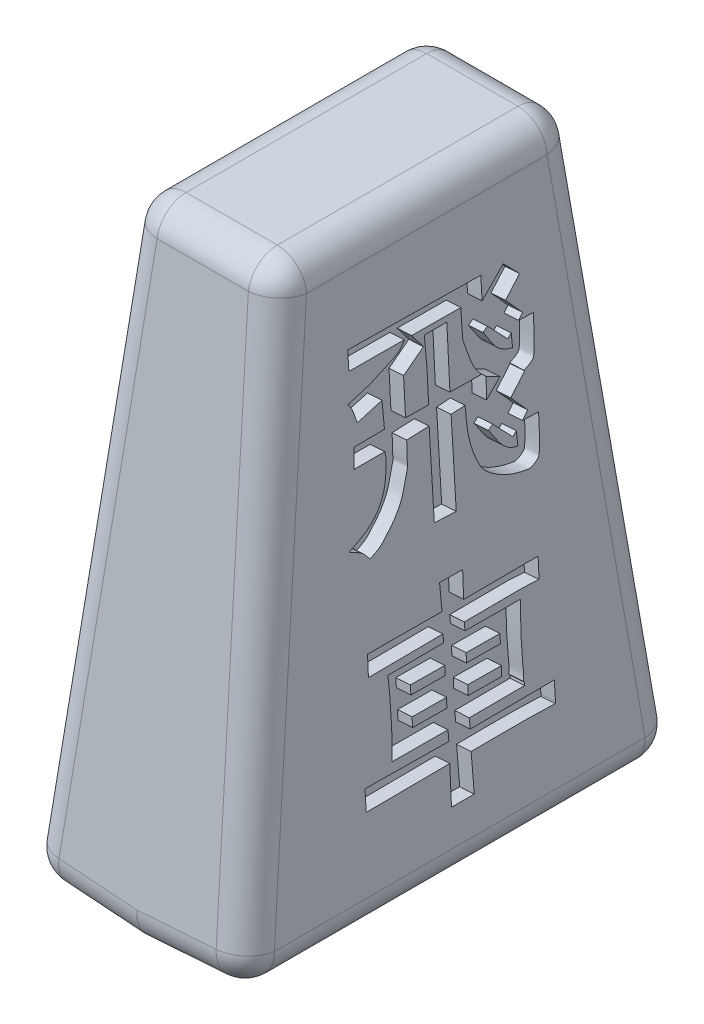
SolidWorks part; units mm, degrees
ref_plane "Płaszczyzna przednia" through (0, 0, 0) normal (0, 0, 1) x (1, 0, 0)
ref_plane "Płaszczyzna górna" through (0, 0, 0) normal (0, 1, 0) x (1, 0, 0)
ref_plane "Płaszczyzna prawa" through (0, 0, 0) normal (1, 0, 0) x (0, 0, -1)
sketch "Szkic1" plane through (0, 0, 0) normal (0, 0, 1) x (1, 0, 0)
  line L0 (0, 0) -> (0, 40)
  line L1 (3.1225, 40) -> (-3.1225, 40)
  line L2 (-5.1185, 38.1262) -> (-7.3738, 2.4704)
  line L3 (-5.504, 0.3481) -> (0, 0)
  line L4 (5.504, 0.3481) -> (0, 0)
  line L5 (5.1185, 38.1262) -> (7.3738, 2.4704)
  arc A0 (-3.1225, 40) -> (-5.1185, 38.1262) centre (-3.1225, 38) ccw
  arc A1 (-7.3738, 2.4704) -> (-5.504, 0.3481) centre (-5.3777, 2.3441) ccw
  arc A2 (7.3738, 2.4704) -> (5.504, 0.3481) centre (5.3777, 2.3441) cw
  arc A3 (3.1225, 40) -> (5.1185, 38.1262) centre (3.1225, 38) cw
  point P7 (-5, 40)
  point P10 (-7.5, 0.4744)
  point P17 (7.5, 0.4744)
  point P18 (5, 40)
  dimension "D5" = 2
  dimension "D1" = 40
  dimension "D2" = 90
  dimension "D3" = 5
  dimension "D4" = 7.5
extrude "Dodanie-wyciągnięcie1" add sketch "Szkic1" along normal blind 30 contours L2 A1 L3 L0 L1 A0 | A3 L1 L0 L4 A2 L5 region at (-3.1441, 18.7866, 0) region at (3.1441, 18.7866, 0)
ref_plane "Płaszczyzna1" through (5.1225, 0, 0) normal (1, 0, 0) x (0, 0, -1)
ref_plane "Płaszczyzna2" through (15.1225, 0, 0) normal (1, 0, 0) x (0, 0, -1)
sketch "Szkic7" plane through (15.1225, 0, 0) normal (1, 0, 0) x (0, 0, -1)
  line L0 (-25, 40) -> (-5, 40)
  line L1 (-30, 40) -> (0, 40) construction
  line L2 (-5, 40) -> (0, 0)
  line L3 (0, 0) -> (-30, 0)
  line L4 (-30, 0) -> (0, 0) construction
  line L5 (-15, 0) -> (-15, 40)
  line L6 (-25, 40) -> (-30, 0)
  line L8 (0, 0) -> (-30, 0)
  line L9 (0, 0) -> (0, 40)
  line L10 (0, 40) -> (-30, 40)
  line L11 (-30, 0) -> (-30, 40)
  dimension "D1" = 10
  dimension "D2" = 15
  dimension "D3" = 40
extrude "Wytnij-wyciągnięcie11" cut sketch "Szkic7" against normal through all and the other way through all contours L11 L6 L10 | L9 L10 L2 region at (15.1225, 26.6667, 28.3333) region at (15.1225, 26.6667, 1.6667)
fillet "Zaokrąglenie2" radius 2 18 edges at (0, 40, 5) (-4.4914, 39.4582, 4.9323) (-6.2461, 20.2983, 2.5373) (-6.8784, 1.022, 0.1278) (-2.752, 0.1741, 0.0218) (2.752, 0.1741, 0.0218) (6.8784, 1.022, 0.1278) (6.2461, 20.2983, 2.5373) (4.4914, 39.4582, 4.9323) (4.4914, 39.4582, 25.0677) (6.2461, 20.2983, 27.4627) (6.8784, 1.022, 29.8722) (2.752, 0.1741, 29.9782) (-2.752, 0.1741, 29.9782) (-6.8784, 1.022, 29.8722) (-6.2461, 20.2983, 27.4627) (-4.4914, 39.4582, 25.0677) (0, 40, 25)
sketch "Szkic8" plane through (-7.5, 0.4744, 0) normal (-0.998, 0.0631, 0) x (0, 0, 1)
  line L0 (341.3333, 1024) -> (1706.6667, 1024) construction
  line L1 (9.2738, 33.1189) -> (18.3738, 32.9989)
  line L2 (18.3738, 32.9989) -> (18.3538, 31.4989)
  line L3 (18.3538, 31.4989) -> (19.9138, 32.8989)
  line L4 (19.9138, 32.8989) -> (20.9538, 31.8389)
  line L5 (20.9538, 31.8389) -> (19.9338, 30.7989)
  line L6 (19.9338, 30.7989) -> (21.0138, 29.5789)
  line L7 (21.0138, 29.5789) -> (20.7338, 29.2589)
  line L8 (20.7338, 29.2589) -> (21.7338, 29.2189)
  line L9 (20.9138, 26.2989) -> (20.9538, 26.2389)
  line L10 (20.9538, 26.2389) -> (19.9338, 25.1789)
  line L11 (19.9338, 25.1789) -> (21.0138, 23.9589)
  line L12 (21.0138, 23.9589) -> (20.6338, 23.5389)
  line L13 (20.6338, 23.5389) -> (21.7338, 23.4989)
  line L14 (16.8738, 26.2389) -> (15.9138, 26.1789)
  line L15 (15.9138, 26.1789) -> (15.9138, 20.5989)
  line L16 (15.9138, 20.5989) -> (14.4138, 20.6589)
  line L17 (14.4138, 20.6589) -> (14.4138, 26.2389)
  line L18 (14.4138, 26.2389) -> (12.8738, 26.1789)
  line L19 (11.3738, 26.2389) -> (9.2738, 26.2389)
  line L20 (9.2738, 26.2389) -> (9.3338, 27.4789)
  line L21 (9.3338, 27.4789) -> (11.4338, 27.4989)
  line L22 (11.4338, 27.4989) -> (11.3738, 29.1989)
  line L23 (11.3738, 29.1989) -> (9.6538, 28.7389)
  line L24 (13.0738, 31.8589) -> (9.2738, 31.8789)
  line L25 (9.2738, 31.8789) -> (9.2738, 33.1189)
  line L26 (13.5738, 31.8589) -> (16.9338, 31.8389)
  line L27 (18.0738, 27.4389) -> (15.9138, 27.4589)
  line L28 (15.9138, 27.4589) -> (15.9538, 31.4789)
  line L29 (15.9538, 31.4789) -> (14.4738, 31.4789)
  line L30 (14.4738, 31.4789) -> (14.4138, 31.4589)
  line L31 (14.4538, 27.4389) -> (12.8738, 27.4589)
  line L32 (12.8738, 27.4589) -> (12.8938, 29.8789)
  line L33 (12.8938, 29.8789) -> (14.3138, 30.8589)
  line L34 (14.3138, 30.8589) -> (13.5738, 31.8589)
  line L35 (18.6338, 29.9389) -> (19.9338, 28.5789)
  line L36 (19.9338, 28.5789) -> (20.1938, 28.7989)
  line L37 (20.1938, 28.7989) -> (20.2338, 27.9189)
  line L38 (18.3338, 29.7189) -> (18.6338, 29.9389)
  line L39 (18.3738, 27.1789) -> (19.2938, 26.7189)
  line L40 (19.2938, 26.7189) -> (18.2938, 25.8389)
  line L41 (18.2938, 25.8389) -> (18.3738, 27.1789)
  line L42 (18.6138, 24.2989) -> (19.9338, 22.9389)
  line L43 (19.9338, 22.9389) -> (20.1738, 23.1589)
  line L44 (20.1738, 23.1589) -> (20.2338, 22.2589)
  line L45 (18.3538, 24.0789) -> (18.3338, 24.0789)
  line L46 (18.3338, 24.0789) -> (18.6138, 24.2789)
  line L47 (18.6138, 24.2789) -> (18.6138, 24.2989)
  line L48 (14.5538, 17.1589) -> (16.1338, 17.1189)
  line L49 (16.1338, 17.1189) -> (16.0938, 15.4389)
  line L50 (16.0938, 15.4389) -> (21.1938, 15.4389)
  line L51 (21.1938, 15.4389) -> (21.1538, 14.1189)
  line L52 (16.0538, 14.1389) -> (16.0938, 13.6389)
  line L53 (16.0938, 13.6389) -> (19.8738, 13.5989)
  line L54 (19.8338, 8.6589) -> (16.0538, 8.6189)
  line L55 (16.0538, 8.6189) -> (16.0938, 7.9789)
  line L56 (16.0938, 7.9789) -> (21.8138, 8.0389)
  line L57 (21.8138, 8.0389) -> (21.7938, 6.6789)
  line L58 (21.7938, 6.6789) -> (16.0538, 6.6789)
  line L59 (16.0538, 6.6789) -> (16.1138, 4.2189)
  line L60 (16.1138, 4.2189) -> (14.5538, 4.2589)
  line L61 (14.5538, 4.2589) -> (14.5938, 6.7189)
  line L62 (14.5938, 6.7189) -> (8.8738, 6.6589)
  line L63 (8.8738, 6.6589) -> (8.9138, 8.0389)
  line L64 (14.6138, 8.0189) -> (14.5738, 8.6589)
  line L65 (14.5738, 8.6589) -> (10.7738, 8.6989)
  line L66 (10.7938, 13.6389) -> (14.6138, 13.6789)
  line L67 (14.6138, 13.6789) -> (14.5738, 14.1789)
  line L68 (14.5738, 14.1789) -> (9.5138, 14.1189)
  line L69 (9.5138, 14.1189) -> (9.5338, 15.4789)
  line L70 (9.5338, 15.4789) -> (14.6138, 15.4789)
  line L71 (14.6138, 15.4789) -> (14.5538, 17.1589)
  line L72 (12.2538, 12.3789) -> (14.6138, 12.3589)
  line L73 (14.6138, 12.3589) -> (14.5938, 11.7789)
  line L74 (14.5938, 11.7789) -> (12.2538, 11.7989)
  line L75 (12.2538, 11.7989) -> (12.2538, 12.3789)
  line L76 (16.0738, 12.3789) -> (18.3938, 12.3589)
  line L77 (18.3938, 12.3589) -> (18.3738, 11.7789)
  line L78 (18.3738, 11.7789) -> (16.0538, 11.7989)
  line L79 (16.0538, 11.7989) -> (16.0738, 12.3789)
  line L80 (12.2538, 10.5389) -> (14.6138, 10.5189)
  line L81 (14.6138, 10.5189) -> (14.5938, 9.8989)
  line L82 (14.5938, 9.8989) -> (12.2538, 9.9189)
  line L83 (12.2538, 9.9189) -> (12.2538, 10.5389)
  line L84 (16.0738, 10.5389) -> (18.3738, 10.5189)
  line L85 (18.3738, 10.5189) -> (18.3538, 9.8989)
  line L86 (18.3538, 9.8989) -> (16.0538, 9.9189)
  line L87 (16.0538, 9.9189) -> (16.0738, 10.5389)
  spline S0 degree 3 poles (21.7338, 29.2189) (21.6938, 28.4189) (21.7556, 27.6073) (21.6138, 26.8189) (21.5631, 26.5367) (21.1305, 26.3937) (20.9138, 26.2989) knots 0 0 0 0 1 1 1 2 2 2 2
  spline S1 degree 3 poles (21.7338, 23.4989) (21.6938, 22.6989) (21.7511, 21.8881) (21.6138, 21.0989) (21.5848, 20.9317) (21.401, 20.8235) (21.2538, 20.7389) (21.1235, 20.664) (20.9627, 20.6174) (20.8138, 20.6389) (20.3497, 20.706) (19.888, 20.8218) (19.4538, 20.9989) (19.0473, 21.1648) (18.6627, 21.3924) (18.3138, 21.6589) (18.0626, 21.8509) (17.8251, 22.0813) (17.6738, 22.3589) (17.2582, 23.1222) (17.0152, 23.9937) (16.9338, 24.8589) (16.8907, 25.3174) (16.8938, 25.7789) (16.8738, 26.2389) knots 0 0 0 0 1 1 1 2 2 2 3 3 3 4 4 4 5 5 5 6 6 6 7 7 7 8 8 8 8
  spline S2 degree 3 poles (12.8738, 26.1789) (12.8405, 25.6056) (12.8125, 25.0319) (12.7738, 24.4589) (12.7724, 24.4379) (12.7603, 24.419) (12.7538, 24.3989) (12.6069, 23.939) (12.5242, 23.4535) (12.3138, 23.0189) (12.1132, 22.6045) (11.8406, 22.2223) (11.5338, 21.8789) (11.2222, 21.53) (10.8458, 21.2428) (10.4738, 20.9589) (10.3364, 20.854) (10.1672, 20.7989) (10.0138, 20.7189) knots 0 0 0 0 1 1 1 2 2 2 3 3 3 4 4 4 5 5 5 6 6 6 6
  spline S3 degree 3 poles (10.0138, 20.7189) (9.8472, 20.9056) (9.7126, 21.1269) (9.5138, 21.2789) (9.2531, 21.4784) (8.9405, 21.5989) (8.6538, 21.7589) knots 0 0 0 0 1 1 1 2 2 2 2
  spline S4 degree 3 poles (8.6538, 21.7589) (9.0738, 21.9789) (9.524, 22.1491) (9.9138, 22.4189) (10.224, 22.6337) (10.5139, 22.8924) (10.7338, 23.1989) (10.9616, 23.5164) (11.1285, 23.8827) (11.2338, 24.2589) (11.3645, 24.7256) (11.3997, 25.2155) (11.4338, 25.6989) (11.4466, 25.8796) (11.3938, 26.0589) (11.3738, 26.2389) knots 0 0 0 0 1 1 1 2 2 2 3 3 3 4 4 4 5 5 5 5
  spline S5 degree 3 poles (9.6538, 28.7389) (9.5605, 29.0256) (9.4916, 29.3214) (9.3738, 29.5989) (9.3037, 29.7642) (9.1872, 29.9056) (9.0938, 30.0589) knots 0 0 0 0 1 1 1 2 2 2 2
  spline S6 degree 3 poles (9.0938, 30.0589) (9.7405, 30.2523) (10.4158, 30.3677) (11.0338, 30.6389) (12.7351, 31.3854) (12.5704, 31.1876) (13.0738, 31.8589) knots 0 0 0 0 1 1 1 2 2 2 2
  spline S7 degree 3 poles (16.9338, 31.8389) (16.9405, 31.2256) (16.9407, 30.6122) (16.9538, 29.9989) (16.954, 29.9895) (16.9716, 29.9881) (16.9738, 29.9789) (17.0221, 29.786) (17.0537, 29.6192) (17.1138, 29.4389) (17.4038, 28.5692) (17.4914, 28.0941) (18.0738, 27.4389) knots 0 0 0 0 1 1 1 2 2 2 3 3 3 4 4 4 4
  spline S8 degree 3 poles (14.4138, 31.4589) (14.4338, 30.8189) (14.4675, 30.1792) (14.4738, 29.5389) (14.4808, 28.8389) (14.4605, 28.1389) (14.4538, 27.4389) knots 0 0 0 0 1 1 1 2 2 2 2
  spline S9 degree 3 poles (20.2338, 27.9189) (19.0646, 28.2112) (18.9385, 28.812) (18.3338, 29.7189) knots 0 0 0 0 1 1 1 1
  spline S10 degree 3 poles (20.2338, 22.2589) (19.1886, 22.449) (18.8732, 23.2998) (18.3538, 24.0789) knots 0 0 0 0 1 1 1 1
  spline S11 degree 3 poles (21.1538, 14.1189) (20.1272, 14.1389) (19.1007, 14.1749) (18.0738, 14.1789) (17.4004, 14.1816) (16.7272, 14.1523) (16.0538, 14.1389) knots 0 0 0 0 1 1 1 2 2 2 2
  spline S12 degree 3 poles (19.8738, 13.5989) (19.8405, 12.6456) (19.7816, 11.6928) (19.7738, 10.7389) (19.7682, 10.0453) (19.8138, 9.3523) (19.8338, 8.6589) knots 0 0 0 0 1 1 1 2 2 2 2
  spline S13 degree 3 poles (8.9138, 8.0389) (9.9005, 8.0189) (10.887, 7.9824) (11.8738, 7.9789) (12.7873, 7.9757) (13.7005, 8.0056) (14.6138, 8.0189) knots 0 0 0 0 1 1 1 2 2 2 2
  spline S14 degree 3 poles (10.7738, 8.6989) (10.8077, 9.6054) (10.8859, 10.5125) (10.8538, 11.4189) (10.8277, 12.1587) (10.8138, 12.8989) (10.7938, 13.6389) knots 0 0 0 0 1 1 1 2 2 2 2
extrude "Wytnij-wyciągnięcie12" cut sketch "Szkic8" against normal blind 1 contours S6 S5 L23 L22 L21 L20 L19 S4 S3 S2 L18 L17 L16 L15 L14 S1 L13 L12 L11 L10 L9 S0 L8 L7 L6 L5 L4 L3 L2 L1 L25 L24 L40 L41 L39 L30 S8 L31 L32 L33 L34 L26 S7 L27 L28 L29 L37 S9 | S14 L65 L64 S13 L63 L62 L61 L60 L59 L58 L57 L56 L55 L54 S12 L53 L52 S11 L51 L50 L49 L48 L71 L70 L69 L68 L67 L66 L86 L87 L84 L85 L82 L83 L80 L81 L78 L79 L76 L77 L74 L75 L72 L73 region at (-5.7894, 27.5195, 15.8388) region at (-6.81, 11.3834, 15.3264)
sketch "Szkic9" plane through (7.5, 0.4744, 0) normal (0.998, 0.0631, 0) x (0, 0, -1)
  line L0 (341.3333, 1024) -> (1706.6667, 1024) construction
  line L1 (-20.694, 33.2496) -> (-11.594, 33.1296)
  line L2 (-11.594, 33.1296) -> (-11.594, 31.6496)
  line L3 (-11.594, 31.6496) -> (-10.054, 33.0496)
  line L4 (-10.054, 33.0496) -> (-9.014, 31.9696)
  line L5 (-9.014, 31.9696) -> (-10.034, 30.9296)
  line L6 (-10.034, 30.9296) -> (-8.954, 29.7096)
  line L7 (-8.954, 29.7096) -> (-9.234, 29.3896)
  line L8 (-9.234, 29.3896) -> (-8.234, 29.3496)
  line L9 (-9.054, 26.4296) -> (-9.014, 26.3696)
  line L10 (-9.014, 26.3696) -> (-10.034, 25.3096)
  line L11 (-10.034, 25.3096) -> (-8.954, 24.0896)
  line L12 (-8.954, 24.0896) -> (-9.334, 23.6696)
  line L13 (-9.334, 23.6696) -> (-8.234, 23.6296)
  line L14 (-13.094, 26.3696) -> (-14.054, 26.3096)
  line L15 (-14.054, 26.3096) -> (-14.054, 20.7296)
  line L16 (-14.054, 20.7296) -> (-15.554, 20.7896)
  line L17 (-15.554, 20.7896) -> (-15.554, 26.3696)
  line L18 (-15.554, 26.3696) -> (-17.094, 26.3096)
  line L19 (-18.594, 26.3696) -> (-20.694, 26.3696)
  line L20 (-20.694, 26.3696) -> (-20.634, 27.6096)
  line L21 (-20.634, 27.6096) -> (-18.534, 27.6296)
  line L22 (-18.534, 27.6296) -> (-18.594, 29.3296)
  line L23 (-18.594, 29.3296) -> (-20.314, 28.8696)
  line L24 (-16.894, 31.9896) -> (-20.694, 32.0096)
  line L25 (-20.694, 32.0096) -> (-20.694, 33.2496)
  line L26 (-16.394, 31.9896) -> (-13.034, 31.9696)
  line L27 (-11.894, 27.5696) -> (-14.054, 27.5896)
  line L28 (-14.054, 27.5896) -> (-14.014, 31.6096)
  line L29 (-14.014, 31.6096) -> (-15.494, 31.6096)
  line L30 (-15.494, 31.6096) -> (-15.554, 31.5896)
  line L31 (-15.514, 27.5696) -> (-17.094, 27.5896)
  line L32 (-17.094, 27.5896) -> (-17.074, 30.0096)
  line L33 (-17.074, 30.0096) -> (-15.654, 30.9896)
  line L34 (-15.654, 30.9896) -> (-16.394, 31.9896)
  line L35 (-11.334, 30.0696) -> (-10.034, 28.7096)
  line L36 (-10.034, 28.7096) -> (-9.774, 28.9296)
  line L37 (-9.774, 28.9296) -> (-9.734, 28.0496)
  line L38 (-11.634, 29.8496) -> (-11.334, 30.0696)
  line L39 (-11.594, 27.3096) -> (-10.674, 26.8496)
  line L40 (-10.674, 26.8496) -> (-11.654, 25.9696)
  line L41 (-11.654, 25.9696) -> (-11.594, 27.3096)
  line L42 (-11.334, 24.4296) -> (-10.034, 23.0696)
  line L43 (-10.034, 23.0696) -> (-9.774, 23.2896)
  line L44 (-9.774, 23.2896) -> (-9.734, 22.3896)
  line L45 (-11.614, 24.2096) -> (-11.634, 24.2096)
  line L46 (-11.634, 24.2096) -> (-11.334, 24.4296)
  line L47 (-15.414, 17.2896) -> (-13.834, 17.2696)
  line L48 (-13.834, 17.2696) -> (-13.874, 15.5696)
  line L49 (-13.874, 15.5696) -> (-8.774, 15.5896)
  line L50 (-8.774, 15.5896) -> (-8.794, 14.2496)
  line L51 (-13.914, 14.2896) -> (-13.894, 13.7696)
  line L52 (-13.894, 13.7696) -> (-10.094, 13.7496)
  line L53 (-10.114, 8.9696) -> (-10.134, 8.7896)
  line L54 (-10.134, 8.7896) -> (-13.914, 8.7696)
  line L55 (-13.914, 8.7696) -> (-13.894, 8.1096)
  line L56 (-13.894, 8.1096) -> (-8.134, 8.1496)
  line L57 (-8.134, 8.1496) -> (-8.134, 6.8896)
  line L58 (-8.134, 6.8896) -> (-8.154, 6.7896)
  line L59 (-13.914, 6.8296) -> (-13.854, 4.3496)
  line L60 (-13.854, 4.3496) -> (-15.354, 4.3496)
  line L61 (-15.354, 4.3496) -> (-15.414, 4.3696)
  line L62 (-15.414, 4.3696) -> (-15.374, 6.8496)
  line L63 (-15.374, 6.8496) -> (-21.094, 6.8096)
  line L64 (-21.094, 6.8096) -> (-21.094, 8.0496)
  line L65 (-21.094, 8.0496) -> (-21.074, 8.1696)
  line L66 (-21.074, 8.1696) -> (-15.354, 8.1096)
  line L67 (-15.354, 8.1096) -> (-15.374, 8.7896)
  line L68 (-15.374, 8.7896) -> (-19.194, 8.8096)
  line L69 (-19.174, 13.7696) -> (-15.354, 13.7896)
  line L70 (-15.354, 13.7896) -> (-15.374, 14.3096)
  line L71 (-15.374, 14.3096) -> (-20.474, 14.2696)
  line L72 (-20.474, 14.2696) -> (-20.454, 15.6096)
  line L73 (-20.454, 15.6096) -> (-15.354, 15.5896)
  line L74 (-15.354, 15.5896) -> (-15.414, 17.2896)
  line L75 (-17.714, 12.5096) -> (-15.354, 12.4896)
  line L76 (-15.354, 12.4896) -> (-15.374, 11.9096)
  line L77 (-15.374, 11.9096) -> (-17.714, 11.9296)
  line L78 (-17.714, 11.9296) -> (-17.714, 12.5096)
  line L79 (-13.894, 12.5096) -> (-11.574, 12.4896)
  line L80 (-11.574, 12.4896) -> (-11.594, 11.9096)
  line L81 (-11.594, 11.9096) -> (-13.914, 11.9296)
  line L82 (-13.914, 11.9296) -> (-13.894, 12.5096)
  line L83 (-17.714, 10.6696) -> (-15.354, 10.6496)
  line L84 (-15.354, 10.6496) -> (-15.374, 10.0296)
  line L85 (-15.374, 10.0296) -> (-17.714, 10.0496)
  line L86 (-17.714, 10.0496) -> (-17.714, 10.6696)
  line L87 (-13.894, 10.6696) -> (-11.594, 10.6496)
  line L88 (-11.594, 10.6496) -> (-11.614, 10.0296)
  line L89 (-11.614, 10.0296) -> (-13.914, 10.0496)
  line L90 (-13.914, 10.0496) -> (-13.894, 10.6696)
  spline S0 degree 3 poles (-8.234, 29.3496) (-8.274, 28.5496) (-8.2122, 27.7379) (-8.354, 26.9496) (-8.4048, 26.6673) (-8.8374, 26.5243) (-9.054, 26.4296) knots 0 0 0 0 1 1 1 2 2 2 2
  spline S1 degree 3 poles (-8.234, 23.6296) (-8.274, 22.8296) (-8.2167, 22.0187) (-8.354, 21.2296) (-8.3831, 21.0624) (-8.5669, 20.9542) (-8.714, 20.8696) (-8.8444, 20.7946) (-9.0051, 20.7481) (-9.154, 20.7696) (-9.6181, 20.8366) (-10.0798, 20.9524) (-10.514, 21.1296) (-10.9205, 21.2955) (-11.3051, 21.523) (-11.654, 21.7896) (-11.9052, 21.9815) (-12.1429, 22.2118) (-12.294, 22.4896) (-12.7184, 23.2699) (-12.957, 24.1646) (-13.034, 25.0496) (-13.0722, 25.4884) (-13.074, 25.9296) (-13.094, 26.3696) knots 0 0 0 0 1 1 1 2 2 2 3 3 3 4 4 4 5 5 5 6 6 6 7 7 7 8 8 8 8
  spline S2 degree 3 poles (-17.094, 26.3096) (-17.2115, 24.2651) (-17.0097, 25.131) (-17.214, 24.5096) (-17.3674, 24.0429) (-17.4557, 23.5496) (-17.674, 23.1096) (-17.8869, 22.6805) (-18.1669, 22.2795) (-18.494, 21.9296) (-19.2495, 21.1212) (-19.3087, 21.1261) (-19.954, 20.8496) knots 0 0 0 0 1 1 1 2 2 2 3 3 3 4 4 4 4
  spline S3 degree 3 poles (-19.954, 20.8496) (-20.1207, 21.0362) (-20.2552, 21.2576) (-20.454, 21.4096) (-20.7148, 21.609) (-21.0273, 21.7296) (-21.314, 21.8896) knots 0 0 0 0 1 1 1 2 2 2 2
  spline S4 degree 3 poles (-21.314, 21.8896) (-20.894, 22.1096) (-20.4438, 22.2797) (-20.054, 22.5496) (-19.7438, 22.7643) (-19.4539, 23.0231) (-19.234, 23.3296) (-19.0063, 23.647) (-18.8393, 24.0134) (-18.734, 24.3896) (-18.6033, 24.8562) (-18.5682, 25.3462) (-18.534, 25.8296) (-18.5212, 26.0102) (-18.574, 26.1896) (-18.594, 26.3696) knots 0 0 0 0 1 1 1 2 2 2 3 3 3 4 4 4 5 5 5 5
  spline S5 degree 3 poles (-20.314, 28.8696) (-20.4073, 29.1562) (-20.4763, 29.452) (-20.594, 29.7296) (-20.6641, 29.8948) (-20.7807, 30.0362) (-20.874, 30.1896) knots 0 0 0 0 1 1 1 2 2 2 2
  spline S6 degree 3 poles (-20.874, 30.1896) (-20.2273, 30.3829) (-19.5521, 30.4984) (-18.934, 30.7696) (-17.2327, 31.5161) (-17.3975, 31.3183) (-16.894, 31.9896) knots 0 0 0 0 1 1 1 2 2 2 2
  spline S7 degree 3 poles (-13.034, 31.9696) (-13.0273, 31.3562) (-13.0272, 30.7428) (-13.014, 30.1296) (-13.0118, 30.0274) (-12.9294, 29.8277) (-12.894, 29.7096) (-12.6332, 28.8401) (-12.4985, 28.2497) (-11.894, 27.5696) knots 0 0 0 0 1 1 1 2 2 2 3 3 3 3
  spline S8 degree 3 poles (-15.554, 31.5896) (-15.534, 30.9362) (-15.5005, 30.2832) (-15.494, 29.6296) (-15.4872, 28.9429) (-15.5073, 28.2562) (-15.514, 27.5696) knots 0 0 0 0 1 1 1 2 2 2 2
  spline S9 degree 3 poles (-9.734, 28.0496) (-10.8918, 28.339) (-11.0249, 28.9359) (-11.634, 29.8496) knots 0 0 0 0 1 1 1 1
  spline S10 degree 3 poles (-9.734, 22.3896) (-10.7706, 22.5781) (-11.0985, 23.4363) (-11.614, 24.2096) knots 0 0 0 0 1 1 1 1
  spline S11 degree 3 poles (-8.794, 14.2496) (-9.1676, 14.2645) (-9.5401, 14.3096) (-9.914, 14.3096) (-11.2473, 14.3096) (-12.5807, 14.2962) (-13.914, 14.2896) knots 0 0 0 0 1 1 1 2 2 2 2
  spline S12 degree 3 poles (-10.094, 13.7496) (-10.1379, 12.9301) (-10.1883, 12.1102) (-10.194, 11.2896) (-10.1976, 10.7694) (-10.1813, 10.249) (-10.154, 9.7296) (-10.1135, 8.9599) (-10.3093, 9.1648) (-10.114, 8.9696) knots 0 0 0 0 1 1 1 2 2 2 3 3 3 3
  spline S13 degree 3 poles (-8.154, 6.7896) (-10.0845, 6.8735) (-11.9609, 6.8392) (-13.914, 6.8296) knots 0 0 0 0 1 1 1 1
  spline S14 degree 3 poles (-19.194, 8.8096) (-19.1721, 9.2765) (-19.118, 9.7422) (-19.114, 10.2096) (-19.1077, 10.9495) (-19.1074, 11.6896) (-19.114, 12.4296) (-19.1176, 12.837) (-19.174, 13.3373) (-19.174, 13.7696) knots 0 0 0 0 1 1 1 2 2 2 3 3 3 3
extrude "Wytnij-wyciągnięcie13" cut sketch "Szkic9" against normal blind 1 contours S6 S5 L23 L22 L21 L20 L19 S4 S3 S2 L18 L17 L16 L15 L14 S1 L13 L12 L11 L10 L9 S0 L8 L7 L6 L5 L4 L3 L2 L1 L25 L24 L40 L41 L39 L30 S8 L31 L32 L33 L34 L26 S7 L27 L28 L29 L37 S9 | S14 L68 L67 L66 L65 L64 L63 L62 L61 L60 L59 S13 L58 L57 L56 L55 L54 L53 S12 L52 L51 S11 L50 L49 L48 L47 L74 L73 L72 L71 L70 L69 L89 L90 L87 L88 L85 L86 L83 L84 L81 L82 L79 L80 L77 L78 L75 region at (5.7754, 27.7407, 14.2935) region at (6.8013, 11.5215, 14.6145)
